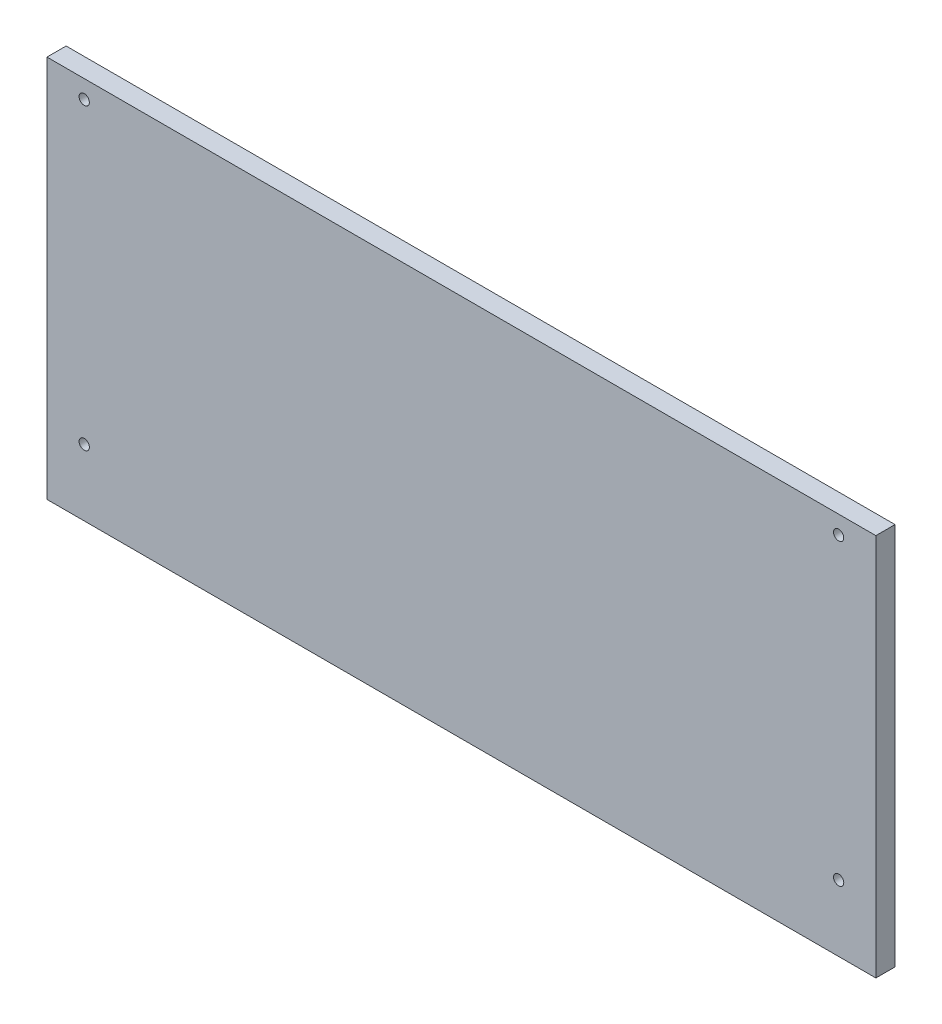
SolidWorks part; units mm, degrees
material "Acrylic (Medium-high impact)"
ref_plane "Front Plane" through (0, 0, 0) normal (0, 0, 1) x (1, 0, 0)
ref_plane "Top Plane" through (0, 0, 0) normal (0, 1, 0) x (1, 0, 0)
ref_plane "Right Plane" through (0, 0, 0) normal (1, 0, 0) x (0, 0, -1)
sketch "Sketch1" plane through (0, 0, 0) normal (0, 0, 1) x (1, 0, 0)
  line L1 (274.7772, 127) -> (0, 127)
  line L2 (274.7772, 127) -> (274.7772, 0)
  line L3 (274.7772, 0) -> (0, 0)
  line L4 (0, 127) -> (0, 0)
  line L5 (274.7772, 127) -> (0, 0) construction
  line L6 (274.7772, 0) -> (0, 127) construction
  point P0 (137.3886, 63.5)
  dimension "D1" = 127
  dimension "D2" = 274.7772
extrude "Boss-Extrude1" add sketch "Sketch1" along normal blind 6.35
hole_wizard "M3 Clearance Hole1" positions "Sketch2" profile "Sketch3" hole size "M3" standard "ANSI Metric" end condition through all
sketch "Sketch2" plane through (0, 0, 6.35) normal (0, 0, 1) x (1, 0, 0)
  line L0 (0, 127) -> (0, 0) construction
  line L1 (274.7772, 127) -> (0, 127) construction
  line L2 (274.7772, 0) -> (274.7772, 127) construction
  line L3 (0, 0) -> (274.7772, 0) construction
  point P0 (12.3444, 121.0056)
  point P2 (12.3444, 21.9964)
  point P4 (262.4328, 21.9964)
  point P6 (262.4328, 121.0056)
  point P29 (0, 0)
  dimension "D1" = 12.3444
  dimension "D2" = 5.9944
  dimension "D3" = 12.3444
  dimension "D4" = 21.9964
sketch "Sketch3" plane through (12.3444, 121.0056, 6.35) normal (1, 0, 0) x (0, -1, 0)
  line L0 (0, 0) -> (0, 6.35)
  line L1 (0, 6.35) -> (1.7, 6.35)
  line L2 (1.7, 6.35) -> (1.7, 0)
  line L5 (1.7, 0) -> (0, 0)
  line L11 (0, -6.35) -> (0, 107.95) construction
  dimension "Thru Hole Dia." = 3.4
  dimension "Thru Hole Depth" = 6.35
sketch "Sketch4" plane through (0, 0, 6.35) normal (0, 0, 1) x (1, 0, 0)
  line L0 (0, 127) -> (0, 0) construction
  line L1 (46.99, 107.95) -> (50.4952, 107.95)
  line L2 (46.99, 107.95) -> (46.99, 31.75)
  line L3 (46.99, 31.75) -> (50.4952, 31.75)
  line L4 (50.4952, 107.95) -> (50.4952, 31.75)
  line L5 (224.282, 107.95) -> (227.7872, 107.95)
  line L6 (224.282, 107.95) -> (224.282, 31.75)
  line L7 (224.282, 31.75) -> (227.7872, 31.75)
  line L8 (227.7872, 107.95) -> (227.7872, 31.75)
  line L9 (274.7772, 0) -> (274.7772, 127) construction
  line L10 (274.7772, 127) -> (0, 127) construction
  dimension "D1" = 3.5052
  dimension "D2" = 76.2
  dimension "D3" = 46.99
  dimension "D4" = 46.99
  dimension "D5" = 19.05
extrude "Cut-Extrude1" [suppressed] cut sketch "Sketch4" against normal through all
sketch "Sketch5" plane through (0, 0, 6.35) normal (0, 0, 1) x (1, 0, 0)
  line L0 (0, 0) -> (274.7772, 0)
  line L1 (274.7772, 0) -> (274.7772, 38.6174)
  line L2 (274.7772, 0) -> (274.7772, 127) construction
  line L3 (274.7772, 38.6174) -> (0, 0)
  dimension "D1" = 8
extrude "Cut-Extrude2" [suppressed] cut sketch "Sketch5" against normal through all
